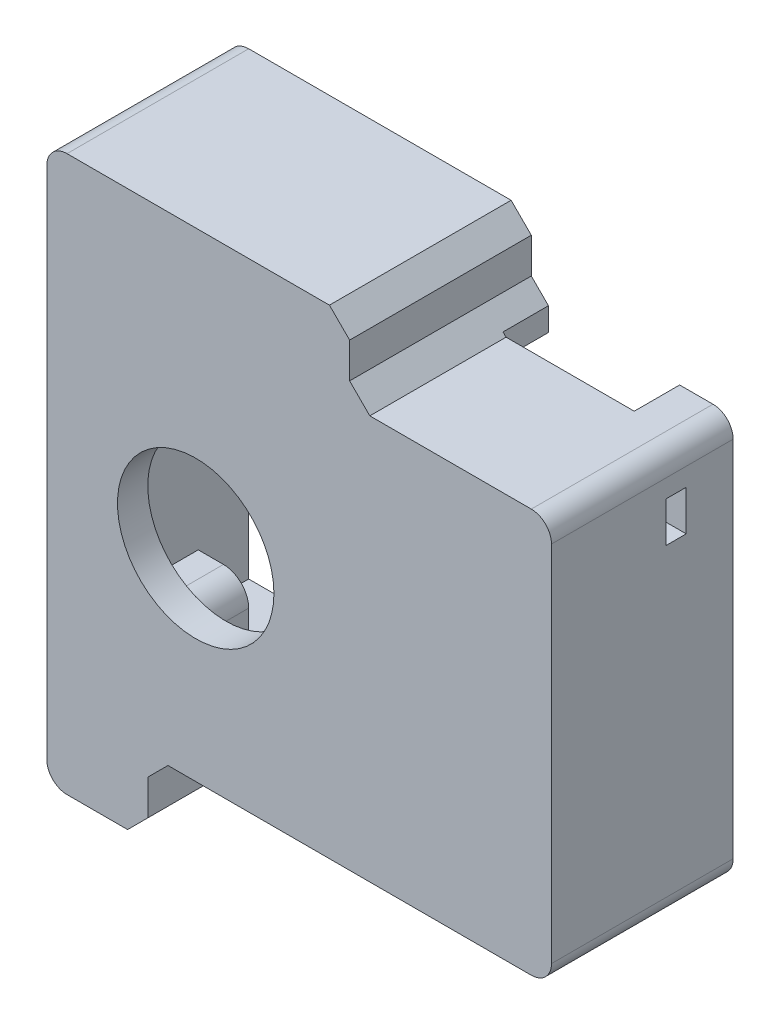
SolidWorks part; units mm, degrees
ref_plane "Front Plane" through (0, 0, 0) normal (0, 0, 1) x (1, 0, 0)
ref_plane "Top Plane" through (0, 0, 0) normal (0, 1, 0) x (1, 0, 0)
ref_plane "Right Plane" through (0, 0, 0) normal (1, 0, 0) x (0, 0, -1)
sketch "Sketch1" plane through (0, 0, 0) normal (0, 0, 1) x (1, 0, 0)
  line L0 (-15, -27.5) -> (-15, -20)
  line L1 (-25, -27.5) -> (-15, -27.5)
  line L2 (-25, -27.5) -> (-25, 27.5)
  line L3 (-25, 27.5) -> (5, 27.5)
  line L4 (25, -20) -> (25, 20)
  line L5 (0, 0) -> (25, 0) construction
  line L6 (0, 0) -> (-25, 0) construction
  line L7 (-23, -18) -> (23, -18)
  line L8 (-23, -18) -> (-23, 18)
  line L9 (-23, 18) -> (23, 18)
  line L10 (23, -18) -> (23, 18)
  line L11 (-23, -18) -> (23, 18) construction
  line L12 (-23, 18) -> (23, -18) construction
  line L13 (-15, -20) -> (25, -20)
  line L14 (5, 27.5) -> (5, 20)
  line L15 (5, 20) -> (25, 20)
  point P0 (0, 0)
  point P1 (-25, 0)
  point P4 (25, 0)
  point P6 (0, 0)
  point P18 (23, 0)
  point P20 (0, 18)
  dimension "D1" = 55
  dimension "D2" = 30
  dimension "D3" = 46
  dimension "D4" = 36
  dimension "D5" = 40
  dimension "D6" = 10
  dimension "D7" = 50
extrude "Boss-Extrude1" add sketch "Sketch1" along normal blind 15
sketch "Sketch2" plane through (0, 0, 15) normal (0, 0, 1) x (1, 0, 0)
  line L12 (-25, 27.5) -> (-25, -27.5)
  line L13 (-25, -27.5) -> (-15, -27.5)
  line L14 (-15, -27.5) -> (-15, -20)
  line L15 (-15, -20) -> (25, -20)
  line L16 (25, -20) -> (25, 20)
  line L17 (25, 20) -> (5, 20)
  line L18 (5, 20) -> (5, 27.5)
  line L19 (5, 27.5) -> (-25, 27.5)
  line L20 (-25, 27.5) -> (-25, -27.5)
  line L21 (-25, -27.5) -> (-15, -27.5)
  line L22 (-15, -27.5) -> (-15, -20)
  line L23 (-15, -20) -> (25, -20)
  line L24 (25, -20) -> (25, 20)
  line L25 (25, 20) -> (5, 20)
  line L26 (5, 20) -> (5, 27.5)
  line L27 (5, 27.5) -> (-25, 27.5)
  dimension "D1" = 0
extrude "Boss-Extrude2" add sketch "Sketch2" along normal blind 3
sketch "Sketch3" plane through (0, 0, 18) normal (0, 0, 1) x (1, 0, 0)
  circle A0 centre (-10.25, 0) radius 7.75
  dimension "D2" = 15.5
  dimension "D3" = 10.25
extrude "Cut-Extrude1" cut sketch "Sketch3" against normal blind 10
sketch "Sketch4" plane through (0, 0, 15) normal (0, 0, -1) x (-1, 0, 0)
  line L0 (18, -18) -> (18, -13)
  line L1 (23, -18) -> (-23, -18) construction
  line L2 (18, -13) -> (23, -13)
  line L3 (23, 18) -> (23, -18) construction
  line L4 (23, -18) -> (23, -13)
  line L5 (23, -18) -> (18, -18)
  line L6 (-23, 18) -> (23, 18) construction
  line L7 (-1.248, -18) -> (-6.248, -18)
  line L8 (-1.248, -18) -> (-1.248, -13)
  line L9 (-1.248, -13) -> (-6.248, -13)
  line L10 (-6.248, -18) -> (-6.248, -13)
  line L11 (-1.248, 18) -> (-6.248, 18)
  line L12 (-1.248, 18) -> (-1.248, 13)
  line L13 (-1.248, 13) -> (-6.248, 13)
  line L14 (-6.248, 18) -> (-6.248, 13)
  line L16 (18, 18) -> (23, 18)
  line L17 (18, 18) -> (18, 13)
  line L18 (18, 13) -> (23, 13)
  line L19 (23, 18) -> (23, 13)
  circle A0 centre (20.252, -15.1962) radius 1
  circle A1 centre (-3.748, -15.1962) radius 1
  circle A2 centre (-3.748, 15.2038) radius 1
  circle A3 centre (20.252, 15.2038) radius 1
  point P36 (-3.748, -18)
  dimension "D1" = 2
  dimension "D2" = 5
  dimension "D4" = 24
  dimension "D5" = 30.4
extrude "Boss-Extrude3" add sketch "Sketch4" along normal blind 10
fillet "Fillet1" radius 2.5 6 edges at (6.248, -13, 10) (1.248, -13, 10) (-18, -13, 10) (-18, 13, 10) (1.248, 13, 10) (6.248, 13, 10)
sketch "Sketch6" plane through (0, 0, -3) normal (0, 0, -1) x (-1, 0, 0)
  line L0 (20, 22.5) -> (20, -22.5) construction
  circle A0 centre (0, 22.5) radius 1
  circle A1 centre (20, 22.5) radius 1
  circle A2 centre (20, -22.5) radius 1
  dimension "D3" = 2
  dimension "D1" = 22.5
  dimension "D2" = 20
  dimension "D4" = 45
extrude "Cut-Extrude2" cut sketch "Sketch6" against normal blind 10
chamfer "Chamfer1" distance 2 angle 45 4 edges at (-15, -27.5, 9) (5, 27.5, 9) (-15, -20, 9) (5, 20, 9)
fillet "Fillet2" radius 2 4 edges at (-25, 27.5, 9) (-25, -27.5, 9) (25, 20, 9) (25, -20, 9)
sketch "Sketch7" plane through (0, 18, 0) normal (0, -1, 0) x (1, 0, 0)
  line L0 (23, 0) -> (-23, 0) construction
  line L1 (6.7, 0) -> (19.7, 0)
  line L2 (6.7, 0) -> (6.7, 4.5)
  line L3 (6.7, 4.5) -> (19.7, 4.5)
  line L4 (19.7, 0) -> (19.7, 4.5)
  point P6 (13.2, 0)
  dimension "D1" = 13
  dimension "D2" = 4.5
  dimension "D3" = 13.2
extrude "Cut-Extrude3" cut sketch "Sketch7" against normal blind 10
sketch "Sketch8" plane through (0, -18, 0) normal (0, 1, 0) x (1, 0, 0)
  line L0 (-23, 0) -> (23, 0) construction
  line L1 (22.2, 0) -> (9.2, 0)
  line L2 (22.2, 0) -> (22.2, -9.5)
  line L3 (22.2, -9.5) -> (11.7, -9.5)
  line L4 (9.2, 0) -> (9.2, -4.5)
  line L5 (11.7, -9.5) -> (11.7, -4.5)
  line L6 (11.7, -4.5) -> (9.2, -4.5)
  line L8 (0.7, -4.2) -> (-8.3, -4.2)
  line L9 (0.7, -4.2) -> (0.7, -8.2)
  line L10 (0.7, -8.2) -> (-8.3, -8.2)
  line L11 (-8.3, -4.2) -> (-8.3, -8.2)
  point P6 (15.7, 0)
  point P14 (-3.8, -4.2)
  dimension "D1" = 13
  dimension "D2" = 15.7
  dimension "D3" = 9.5
  dimension "D4" = 10.5
  dimension "D5" = 4.5
  dimension "D6" = 3.8
  dimension "D7" = 9
  dimension "D8" = 4.2
  dimension "D9" = 4
extrude "Cut-Extrude4" cut sketch "Sketch8" against normal blind 10
sketch "Sketch9" plane through (23, 0, 0) normal (-1, 0, 0) x (0, 0, 1)
  line L1 (4.65, 12.2) -> (6.65, 12.2)
  line L2 (4.65, 12.2) -> (4.65, 16.2)
  line L3 (4.65, 16.2) -> (6.65, 16.2)
  line L4 (6.65, 12.2) -> (6.65, 16.2)
  point P4 (4.65, 14.2)
  dimension "D1" = 2
  dimension "D2" = 4.65
  dimension "D3" = 14.2
  dimension "D4" = 4
extrude "Cut-Extrude5" cut sketch "Sketch9" against normal blind 10
